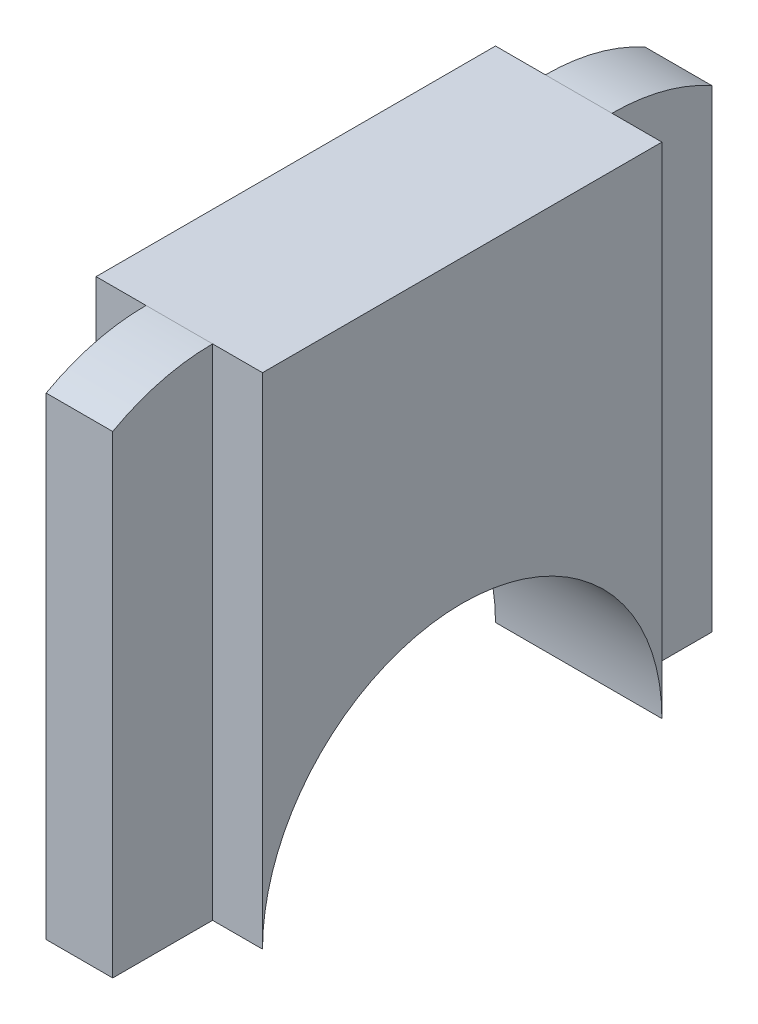
SolidWorks part; units mm, degrees
ref_plane "Front Plane" through (0, 0, 0) normal (0, 0, 1) x (1, 0, 0)
ref_plane "Top Plane" through (0, 0, 0) normal (0, 1, 0) x (1, 0, 0)
ref_plane "Right Plane" through (0, 0, 0) normal (1, 0, 0) x (0, 0, -1)
sketch "Sketch1" plane through (0, 0, 0) normal (1, 0, 0) x (0, 0, -1)
  line L0 (0, 0) -> (0, 15.8754) construction
  line L1 (-6, 15) -> (6, 15)
  line L2 (-6, 15) -> (-6, 0)
  line L3 (-6, 0) -> (6, 0)
  line L4 (6, 15) -> (6, 0)
  line L6 (-6, 15) -> (-6, 0)
  line L7 (-6, 0) -> (-9, 0)
  line L10 (9, 14.22) -> (9, 0)
  line L11 (6, 0) -> (9, 0)
  line L12 (-9, 14.22) -> (-9, 0)
  arc A0 (-6, 0) -> (6, 0) centre (0, 0) cw
  arc A1 (-6, 15) -> (-9, 14.22) centre (-6, 8.8408) ccw
  arc A2 (6, 15) -> (9, 14.22) centre (6, 8.8408) cw
  point P4 (0, 0)
  point P16 (-6, 5)
  dimension "D1" = 15
  dimension "D2" = 12
  dimension "D3" = 3
  dimension "D4" = 0.78
extrude "Boss-Extrude1" add sketch "Sketch1" along normal blind 2.5 and the other way blind 2.5 contours A0 L0 L1 L2 | L0 A0 L4 L1 region at (0, 9.769, 3.2077) region at (0, 9.769, -3.2077)
extrude "Boss-Extrude2" add sketch "Sketch1<3>" along normal blind 1 and the other way blind 1 contours L12 L7 L2 | L4 L11 L10 region at (0, 7.3753, 7.487) region at (0, 7.3753, -7.487)
sketch "Sketch1<3>" plane through (0, 0, 0) normal (1, 0, 0) x (0, 0, -1) same geometry as "Sketch1"
